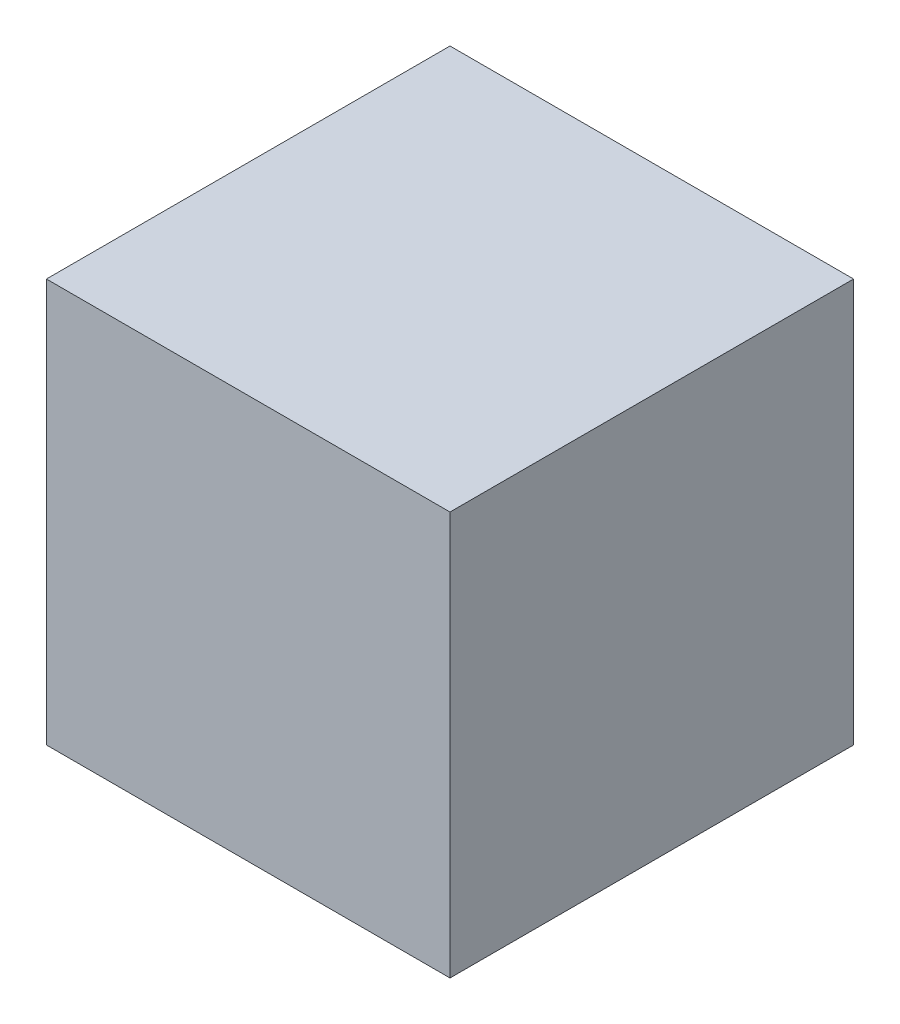
SolidWorks part; units mm, degrees
ref_plane "Front Plane" through (0, 0, 0) normal (0, 0, 1) x (1, 0, 0)
ref_plane "Top Plane" through (0, 0, 0) normal (0, 1, 0) x (1, 0, 0)
ref_plane "Right Plane" through (0, 0, 0) normal (1, 0, 0) x (0, 0, -1)
sketch "Sketch1" plane through (0, 0, 0) normal (0, 1, 0) x (1, 0, 0)
  line L1 (-114.3, -101.6) -> (88.9, -101.6)
  line L2 (-114.3, -101.6) -> (-114.3, 101.6)
  line L3 (-114.3, 101.6) -> (88.9, 101.6)
  line L4 (88.9, -101.6) -> (88.9, 101.6)
  line L5 (-114.3, -101.6) -> (88.9, 101.6) construction
  line L6 (-114.3, 101.6) -> (88.9, -101.6) construction
  point P0 (-12.7, 0)
  point P6 (-12.1439, 0)
  point P8 (0, 0)
  dimension "D1" = 203.2
  dimension "D2" = 203.2
  dimension "D3" = 12.7
extrude "Boss-Extrude1" add sketch "Sketch1" along normal blind 203.2
sketch "Sketch2" plane through (0, 0, 0) normal (0, 1, 0) x (1, 0, 0)
  line L1 (-46.482, -38.9001) -> (46.482, -38.9001)
  line L2 (-46.482, -38.9001) -> (-46.482, 38.9001)
  line L3 (-46.482, 38.9001) -> (46.482, 38.9001)
  line L4 (46.482, -38.9001) -> (46.482, 38.9001)
  line L5 (-46.482, -38.9001) -> (46.482, 38.9001) construction
  line L6 (-46.482, 38.9001) -> (46.482, -38.9001) construction
  point P0 (0, 0)
  dimension "D1" = 92.964
  dimension "D2" = 77.8002
extrude "Boss-Extrude2" add sketch "Sketch2" along normal blind 20.32 separate body
sketch "Boat Sketch" plane through (0, 0, 0) normal (0, 0, 1) x (1, 0, 0)
  line L0 (-114.3, 0) -> (88.9, 0) construction
  line L2 (-46.482, 0) -> (46.482, 0) construction
  line L3 (-46.482, 20.32) -> (46.482, 20.32) construction
  arc A0 (46.482, 0) -> (56.0914, 11.5009) centre (59.1552, -0.8239) cw
  arc A1 (56.0914, 11.5009) -> (71.882, 25.4) centre (50.5765, 33.6857) ccw
  arc A2 (56.0914, 11.5009) -> (-54.102, 6.35) centre (-11.9132, 285.0613) cw
  arc A3 (-46.482, 0) -> (-54.102, 6.35) centre (-57.7768, -5.8067) ccw
  arc A4 (-54.102, 6.35) -> (-66.802, 28.575) centre (-103.1359, -6.9283) ccw
  arc A5 (-66.802, 28.575) -> (-54.102, 27.5646) centre (-77.5674, -187.0564) cw
  arc A6 (-54.102, 27.5646) -> (71.882, 25.4) centre (20.6566, 711.327) ccw
  point P34 (0, 0)
  point P35 (-54.102, 27.8311)
  point P36 (-68.1031, 30.2329)
  point P39 (-57.7768, 28.575)
  point P40 (-54.102, 27.5645)
  dimension "D3" = 22.86
  dimension "D6" = 12.7
  dimension "D11" = 50.8
  dimension "D12" = 215.9
  dimension "D1" = 25.4
  dimension "D2" = 25.4
  dimension "D4" = 7.62
  dimension "D5" = 6.35
  dimension "D7" = 3.175
  dimension "D8" = 28.575
  dimension "D9" = 3.1699
  dimension "D10" = 20.32
sketch "Balloon Sketch" plane through (0, 0, 0) normal (0, 0, 1) x (1, 0, 0)
  line L0 (-72.295, 139.7) -> (49927.705, 139.7) construction
  line L1 (0, 0) -> (0, 50000) construction
  line L2 (-19.05, 198.12) -> (19.05, 198.12) construction
  line L3 (-69.85, 117.5813) -> (-69.85, 179.9578) construction
  line L4 (-69.85, 117.5813) -> (-91.6467, 146.7913)
  line L6 (-114.3, 203.2) -> (-114.3, 0) construction
  arc A0 (76.1755, 152.0409) -> (-76.1755, 152.0409) centre (0, 109.6962) ccw
  arc A1 (-76.1755, 127.3591) -> (76.1755, 127.3591) centre (0, 169.7037) ccw
  arc A2 (-76.1755, 152.0409) -> (-76.1755, 127.3591) centre (-53.975, 139.7) ccw
  arc A3 (76.1755, 152.0409) -> (76.1755, 127.3591) centre (53.975, 139.7) cw
  arc A4 (-34.925, 89.8538) -> (-19.05, 63.5) centre (-68.4593, 51.695) cw
  arc A5 (-19.05, 198.12) -> (19.05, 198.12) centre (0, 137.5449) cw
  arc A6 (-91.6467, 146.7913) -> (-57.15, 175.4964) centre (-17.28, 92.5012) cw
  arc A7 (-69.85, 117.5813) -> (-88.392, 125.9633) centre (-96.407, 83.5336) ccw
  arc A8 (-88.392, 125.9633) -> (-114.3, 146.7913) centre (-125.0176, 106.932) ccw
  arc A9 (-114.3, 146.7913) -> (-57.15, 175.4964) centre (-36.4711, 63.0825) cw
  point P10 (0, 82.55)
  point P14 (-81.8263, 139.7)
  point P17 (81.8263, 139.7)
  point P22 (0, 201.0449)
  point P29 (-114.3, 146.8055)
  point P36 (-88.4651, 125.7422)
  point P37 (-16.1504, 50.419)
  dimension "D2" = 25.4
  dimension "D3" = 158.75
  dimension "D4" = 114.3
  dimension "D7" = 38.1
  dimension "D11" = 63.5
  dimension "D13" = 18.542
  dimension "D15" = 43.18
  dimension "D17" = 41.275
  dimension "D18" = 92.075
  dimension "D19" = 114.3
  dimension "D8" = 50.8
  dimension "D1" = 139.7
  dimension "D5" = 69.85
  dimension "D6" = 63.5
  dimension "D9" = 38.1
  dimension "D10" = 58.42
  dimension "D12" = 69.85
  dimension "D14" = 8.382
  dimension "D16" = 29.21
  dimension "D20" = 12.7
sketch "Engine Sketch" plane through (0, 0, 0) normal (0, 0, 1) x (1, 0, 0)
  line L0 (-6.35, 71.12) -> (-6.35, 45.72)
  line L1 (-6.35, 45.72) -> (-15.875, 45.72)
  line L2 (-15.875, 45.72) -> (-25.4071, 29.21)
  line L3 (-25.4071, 29.21) -> (-57.1571, 29.21)
  line L4 (6.35, 71.12) -> (6.35, 45.72)
  line L5 (6.35, 45.72) -> (15.875, 45.72)
  line L6 (15.875, 45.72) -> (22.225, 34.7215)
  line L7 (22.225, 34.7215) -> (22.225, 22.86)
  line L8 (-57.1571, 29.21) -> (-57.1571, 22.86)
  line L9 (0, 0) -> (0, 50000) construction
  line L11 (-114.3, 0) -> (88.9, 0) construction
  point P13 (-20.0024, 47.494)
  point P14 (29.5473, 34.1537)
  point P18 (21.4478, 38.7593)
  point P19 (22.8771, 33.9949)
  dimension "D1" = 12.7
  dimension "D2" = 9.525
  dimension "D3" = 22.86
  dimension "D4" = 60
  dimension "D5" = 60
  dimension "D6" = 45.72
  dimension "D7" = 25.4
  dimension "D8" = 22.225
  dimension "D9" = 6.35
  dimension "D10" = 31.75
